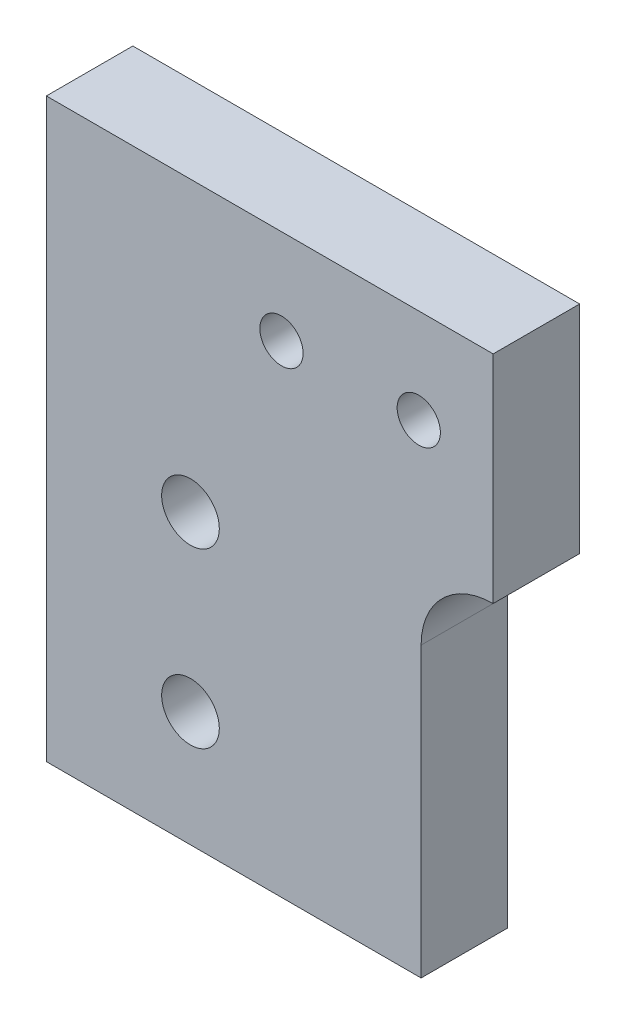
SolidWorks part; units mm, degrees
ref_plane "Plano frontal" through (0, 0, 0) normal (0, 0, 1) x (1, 0, 0)
ref_plane "Plano superior" through (0, 0, 0) normal (0, 1, 0) x (1, 0, 0)
ref_plane "Plano direito" through (0, 0, 0) normal (1, 0, 0) x (0, 0, -1)
sketch "Esboço1" plane through (0, 0, 0) normal (0, 0, 1) x (1, 0, 0)
  line L1 (-15.5, 20) -> (15.5, 20)
  line L2 (-15.5, 20) -> (-15.5, -20)
  line L3 (-15.5, -20) -> (15.5, -20)
  line L4 (15.5, 20) -> (15.5, -20)
  line L5 (-15.5, 20) -> (15.5, -20) construction
  line L6 (-15.5, -20) -> (15.5, 20) construction
  point P0 (0, 0)
  dimension "D1" = 31
  dimension "D2" = 40
extrude "Ressalto-extrusão1" add sketch "Esboço1" along normal blind 6
sketch "Esboço2" plane through (0, 0, 6) normal (0, 0, 1) x (1, 0, 0)
  line L1 (15.5, -20) -> (10.5, -20)
  line L2 (15.5, -20) -> (15.5, 5)
  line L3 (15.5, 5) -> (10.5, 5)
  line L4 (10.5, -20) -> (10.5, 5)
  line L5 (-15.5, -20) -> (15.5, -20) construction
  line L6 (-5.5, 20) -> (-5.5, -20)
  line L7 (-5.5, 20) -> (-5.5, -20) construction
  line L8 (15.5, 20) -> (-15.5, 20) construction
  circle A0 centre (-5.5, -12) radius 2
  circle A1 centre (-5.5, 0) radius 2
  point P13 (0, 0)
  dimension "D4" = 4
  dimension "D1" = 5
  dimension "D2" = 15
  dimension "D5" = 8
  dimension "D6" = 12
  dimension "D3" = 10
extrude "Corte-extrusão1" cut sketch "Esboço2" against normal up to surface (6 mm away) up to face at (0, 0, 0)
sketch "Esboço4" plane through (0, 0, 6) normal (0, 0, 1) x (1, 0, 0)
  circle A0 centre (0.8125, 13.4375) radius 1.175 construction
  circle A1 centre (10.3375, 13.4375) radius 1.175 construction
  circle A2 centre (0.8125, 13.4375) radius 1.175 construction
  circle A3 centre (10.3375, 13.4375) radius 1.175 construction
  circle A4 centre (0.8125, 13.4375) radius 1.5
  circle A5 centre (10.3375, 13.4375) radius 1.5
  dimension "D2" = 3
extrude "Corte-extrusão2" cut sketch "Esboço4" against normal up to surface (6 mm away) up to face at (-3.5, -12, 0)
sketch "Esboço5" plane through (0, 0, 0) normal (0, 0, -1) x (-1, 0, 0)
  circle A0 centre (-0.8125, 13.4375) radius 2.5
  circle A1 centre (-10.3375, 13.4375) radius 2.5
  dimension "D1" = 5
extrude "Corte-extrusão3" cut sketch "Esboço5" against normal blind 2.4
fillet "Filete1" radius 5 1 edges at (10.5, 5, 3)
